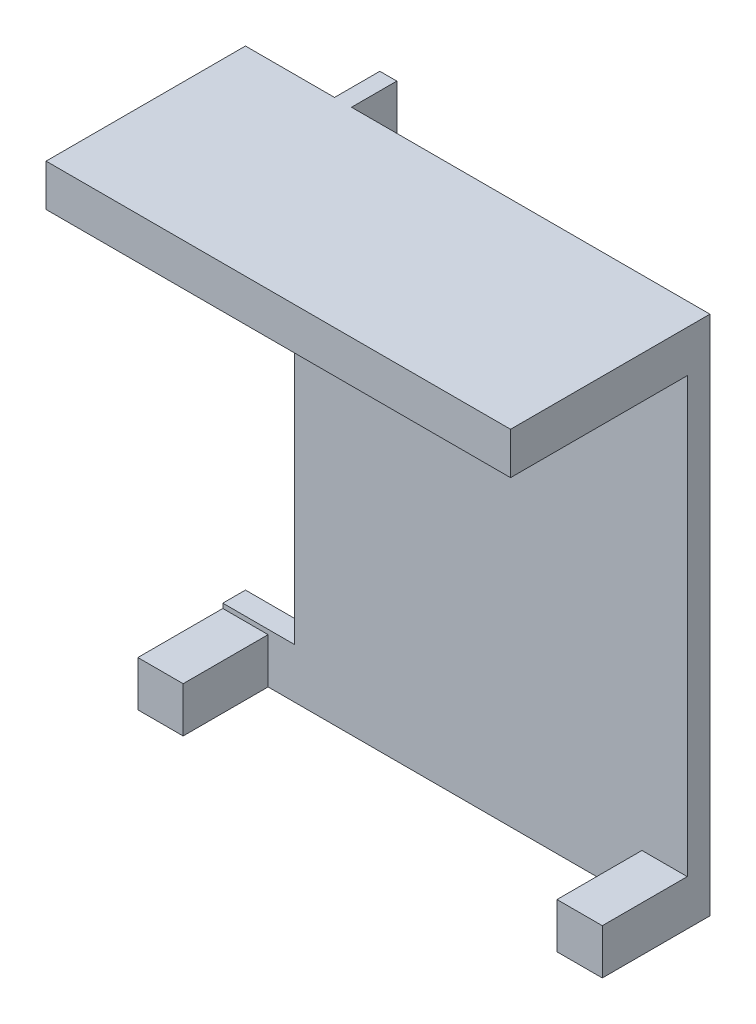
SolidWorks part; units mm, degrees
ref_plane "Piano frontale" through (0, 0, 0) normal (0, 0, 1) x (1, 0, 0)
ref_plane "Piano superiore" through (0, 0, 0) normal (0, 1, 0) x (1, 0, 0)
ref_plane "Piano destro" through (0, 0, 0) normal (1, 0, 0) x (0, 0, -1)
sketch "Schizzo1" plane through (0, 0, 0) normal (0, 0, 1) x (1, 0, 0)
  line L1 (0, 0) -> (41, 0)
  line L2 (0, 0) -> (0, 46)
  line L3 (0, 46) -> (41, 46)
  line L4 (41, 0) -> (41, 46)
  dimension "D1" = 41
  dimension "D2" = 46
extrude "Estrusione-Estrusione1" add sketch "Schizzo1" along normal blind 2
sketch "Schizzo2" plane through (0, 0, 2) normal (0, 0, 1) x (1, 0, 0)
  line L1 (0, 0) -> (4, 0)
  line L2 (0, 0) -> (0, 4)
  line L3 (0, 4) -> (4, 4)
  line L4 (4, 0) -> (4, 4)
  line L5 (41, 0) -> (37, 0)
  line L6 (41, 0) -> (41, 4)
  line L7 (41, 4) -> (37, 4)
  line L8 (37, 0) -> (37, 4)
  dimension "D1" = 4
  dimension "D2" = 4
  dimension "D3" = 4
  dimension "D4" = 4
extrude "Estrusione-Estrusione2" add sketch "Schizzo2" along normal blind 7.5
sketch "Schizzo3" plane through (0, 0, 2) normal (0, 0, 1) x (1, 0, 0)
  line L0 (41, 4) -> (41, 46) construction
  line L1 (0, 46) -> (41, 46)
  line L2 (0, 46) -> (0, 42.3)
  line L3 (0, 42.3) -> (41, 42.3)
  line L4 (41, 46) -> (41, 42.3)
  dimension "D1" = 3.7
extrude "Estrusione-Estrusione3" add sketch "Schizzo3" along normal blind 15.6
sketch "Schizzo4" plane through (0, 0, 0) normal (0, 0, -1) x (-1, 0, 0)
  line L0 (0, 46) -> (0, 0) construction
  line L1 (0, 38.7495) -> (-6.3157, 38.7495)
  line L2 (0, 38.7495) -> (0, 4.408)
  line L3 (0, 4.408) -> (-6.3157, 4.408)
  line L4 (-6.3157, 38.7495) -> (-6.3157, 4.408)
extrude "Taglio-Estrusione1" cut sketch "Schizzo4" against normal blind 2
sketch "Schizzo5" plane through (0, 0, 0) normal (0, 0, -1) x (-1, 0, 0)
  line L0 (-41, 46) -> (0, 46) construction
  line L1 (-9.3615, 46) -> (-7.8615, 46)
  line L2 (-9.3615, 46) -> (-9.3615, 32)
  line L3 (-9.3615, 32) -> (-7.8615, 32)
  line L4 (-7.8615, 46) -> (-7.8615, 32)
  dimension "D1" = 1.5
  dimension "D2" = 14
extrude "Estrusione-Estrusione4" add sketch "Schizzo5" along normal blind 4
